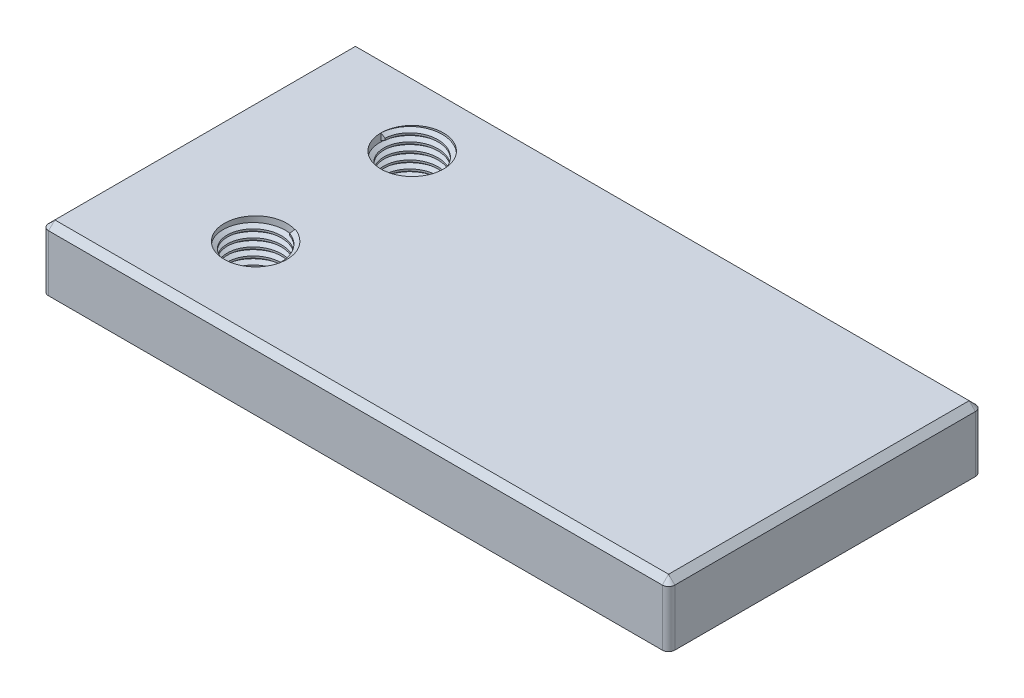
SolidWorks part; units mm, degrees
ref_plane "Alzado" through (0, 0, 0) normal (0, 0, 1) x (1, 0, 0)
ref_plane "Planta" through (0, 0, 0) normal (0, 1, 0) x (1, 0, 0)
ref_plane "Vista lateral" through (0, 0, 0) normal (1, 0, 0) x (0, 0, -1)
sketch "Croquis1" plane through (0, 0, 0) normal (0, 1, 0) x (1, 0, 0)
  line L1 (-49, 25) -> (49, 25)
  line L2 (-50, 24) -> (-50, -24)
  line L3 (-49, -25) -> (49, -25)
  line L4 (50, 24) -> (50, -24)
  line L5 (-50, 25) -> (50, -25) construction
  line L6 (-50, -25) -> (50, 25) construction
  arc A0 (49, 25) -> (50, 24) centre (49, 24) cw
  arc A1 (49, -25) -> (50, -24) centre (49, -24) ccw
  arc A2 (-50, -24) -> (-49, -25) centre (-49, -24) ccw
  arc A3 (-49, 25) -> (-50, 24) centre (-49, 24) ccw
  point P0 (0, 0)
  dimension "D3" = 1
  dimension "D1" = 100
  dimension "D2" = 50
extrude "Saliente-Extruir1" add sketch "Croquis1" along normal blind 10
chamfer "Chaflán1" distance 1 angle 45 8 edges at (-49.7071, 10, -24.7071) (-50, 10, 0) (-49.7071, 10, 24.7071) (0, 10, -25) (49.7071, 10, -24.7071) (50, 10, 0) (49.7071, 10, 24.7071) (0, 10, 25)
sketch "Croquis3" plane through (0, 10, 0) normal (0, 1, 0) x (1, 0, 0)
  line L0 (-50, -24) -> (-50, 24) construction
  circle A0 centre (-30, 14.062) radius 5
  circle A1 centre (-30, -10.938) radius 5
  dimension "D4" = 10
  dimension "D5" = 10
  dimension "D1" = 20
  dimension "D2" = 25
  dimension "D3" = 20
extrude "Cortar-Extruir1" cut sketch "Croquis3" against normal blind 10
thread "Rosca1" pitch 1.25 method extrude profile "Perfil de rosca1" start angle 0, offset 0, length 9, pitch 1.25, diameter 10
ref_plane "Plano2" through (-25, 0, 10.938) normal (0, 0, 1) x (1, 0, 0)
sketch "Perfil de rosca1" plane through (-25, 0, 10.938) normal (0, 0, 1) x (1, 0, 0)
  line L0 (0, 0) -> (0, 1.25) construction
  line L11 (0, 0) -> (0, 1.0937)
  line L12 (0, 1.0937) -> (-0.6766, 0.7031)
  line L13 (-0.6766, 0.7031) -> (-0.6766, 0.3906)
  line L15 (-0.6766, 0.3906) -> (0, 0)
  line L17 (-0.6766, 0.5469) -> (0, 0.5469) construction
  point P2 (0, 0)
  dimension "Pitch" = 1.25
  dimension "Profile_Angle" = 60
  dimension "Profile_Land" = 0.3125
  dimension "Profile_Height" = 0.6766
thread "Rosca3" pitch 1.25 method extrude profile "Perfil de rosca3" start angle 0, offset 0, length 9, pitch 1.25, diameter 10
ref_plane "Plano4" through (-35, 10, -14.062) normal (0, 0, 1) x (-1, 0, 0)
sketch "Perfil de rosca3" plane through (-35, 10, -14.062) normal (0, 0, 1) x (-1, 0, 0)
  line L0 (0, 0) -> (0, 1.25) construction
  line L11 (0, 0) -> (0, 1.0937)
  line L12 (0, 1.0937) -> (-0.6766, 0.7031)
  line L13 (-0.6766, 0.7031) -> (-0.6766, 0.3906)
  line L15 (-0.6766, 0.3906) -> (0, 0)
  line L17 (-0.6766, 0.5469) -> (0, 0.5469) construction
  point P2 (0, 0)
  dimension "Pitch" = 1.25
  dimension "Profile_Angle" = 60
  dimension "Profile_Land" = 0.3125
  dimension "Profile_Height" = 0.6766
